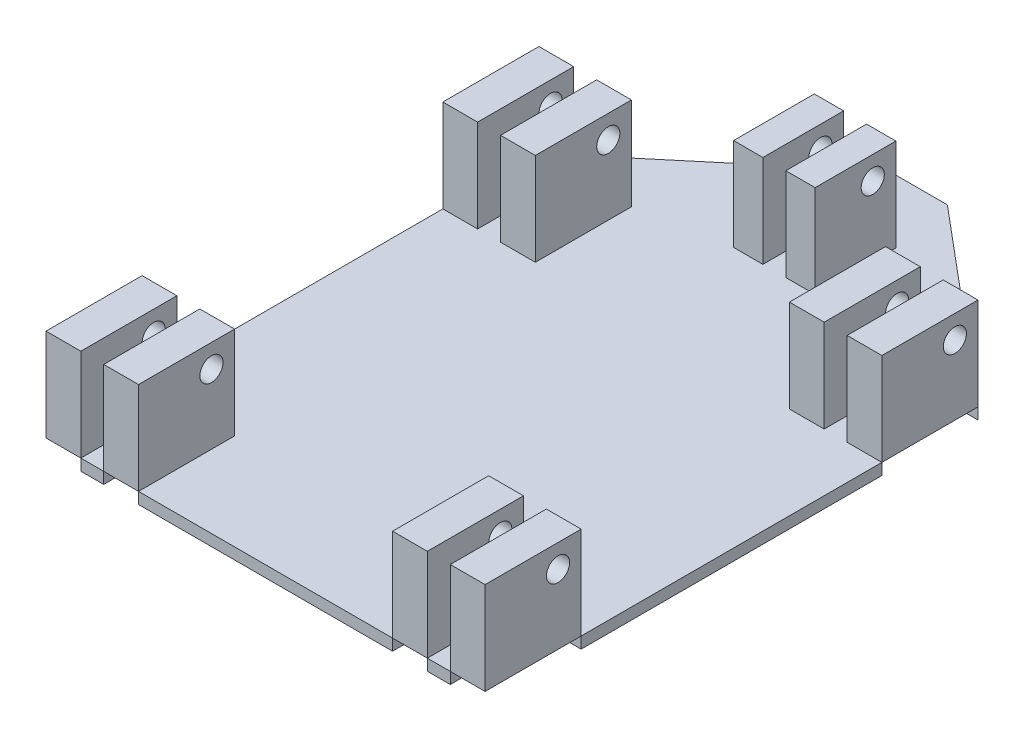
SolidWorks part; units mm, degrees
ref_plane "Front Plane" through (0, 0, 0) normal (0, 0, 1) x (1, 0, 0)
ref_plane "Top Plane" through (0, 0, 0) normal (0, 1, 0) x (1, 0, 0)
ref_plane "Right Plane" through (0, 0, 0) normal (1, 0, 0) x (0, 0, -1)
sketch "Sketch3" plane through (0, 0, 0) normal (0, 1, 0) x (1, 0, 0)
  line L0 (0, -106.5039) -> (0, 106.5039) construction
  line L1 (94.869, -106.5039) -> (-94.869, -106.5039)
  line L2 (94.869, -106.5039) -> (94.869, 106.5039)
  line L3 (94.869, 106.5039) -> (-94.869, 106.5039)
  line L4 (-94.869, -106.5039) -> (-94.869, 106.5039)
  line L5 (94.869, -106.5039) -> (-94.869, 106.5039) construction
  line L6 (94.869, 106.5039) -> (-94.869, -106.5039) construction
  line L7 (-94.869, 106.5039) -> (-79.8332, 106.5039)
  line L8 (-94.869, 106.5039) -> (-94.869, 64.9763)
  line L9 (-94.869, 64.9763) -> (-79.8332, 64.9763)
  line L10 (-79.8332, 106.5039) -> (-79.8332, 64.9763)
  line L11 (-94.869, 106.5039) -> (-79.8332, 64.9763) construction
  line L12 (-94.869, 64.9763) -> (-79.8332, 106.5039) construction
  line L13 (-74.8802, -106.5039) -> (74.8802, -106.5039)
  line L14 (74.8802, -106.5039) -> (74.8802, 106.5039) construction
  line L15 (-94.869, 0) -> (94.869, 0) construction
  line L16 (-74.8802, -106.5039) -> (-74.8802, 106.5039) construction
  line L17 (-54.8913, 64.9763) -> (-69.9272, 64.9763)
  line L18 (-69.9272, 106.5039) -> (-69.9272, 64.9763)
  line L19 (-54.8913, 106.5039) -> (-69.9272, 106.5039)
  line L20 (-54.8913, 106.5039) -> (-54.8913, 64.9763)
  line L21 (-54.8913, -106.5039) -> (-54.8913, -64.9763)
  line L22 (-54.8913, -106.5039) -> (-69.9272, -106.5039)
  line L23 (-69.9272, -106.5039) -> (-69.9272, -64.9763)
  line L24 (-54.8913, -64.9763) -> (-69.9272, -64.9763)
  line L25 (-94.869, -64.9763) -> (-79.8332, -64.9763)
  line L26 (-79.8332, -106.5039) -> (-79.8332, -64.9763)
  line L27 (-94.869, -106.5039) -> (-79.8332, -106.5039)
  line L28 (-94.869, -106.5039) -> (-94.869, -64.9763)
  line L29 (94.869, -106.5039) -> (79.8332, -106.5039)
  line L30 (79.8332, -106.5039) -> (79.8332, -64.9763)
  line L31 (94.869, -64.9763) -> (79.8332, -64.9763)
  line L32 (94.869, -106.5039) -> (94.869, -64.9763)
  line L33 (54.8913, -106.5039) -> (69.9272, -106.5039)
  line L34 (69.9272, -106.5039) -> (69.9272, -64.9763)
  line L35 (54.8913, -64.9763) -> (69.9272, -64.9763)
  line L36 (54.8913, -106.5039) -> (54.8913, -64.9763)
  line L37 (54.8913, 106.5039) -> (54.8913, 64.9763)
  line L38 (54.8913, 106.5039) -> (69.9272, 106.5039)
  line L39 (69.9272, 106.5039) -> (69.9272, 64.9763)
  line L40 (54.8913, 64.9763) -> (69.9272, 64.9763)
  line L41 (94.869, 64.9763) -> (79.8332, 64.9763)
  line L42 (79.8332, 106.5039) -> (79.8332, 64.9763)
  line L43 (94.869, 106.5039) -> (79.8332, 106.5039)
  line L44 (94.869, 106.5039) -> (94.869, 64.9763)
  line L45 (-94.869, 106.5039) -> (-12.6358, 175.5058)
  line L46 (-12.6358, 175.5058) -> (12.6358, 175.5058)
  line L47 (12.6358, 175.5058) -> (94.869, 106.5039)
  line L48 (-45.1068, 148.2593) -> (45.1068, 148.2593)
  line L49 (17.6268, 113.3764) -> (4.953, 148.2593) construction
  line L50 (-17.6268, 148.2593) -> (-4.953, 148.2593)
  line L51 (-17.6268, 148.2593) -> (-17.6268, 113.3764)
  line L52 (-17.6268, 113.3764) -> (-4.953, 113.3764)
  line L53 (-4.953, 148.2593) -> (-4.953, 113.3764)
  line L54 (-17.6268, 148.2593) -> (-4.953, 113.3764) construction
  line L55 (-17.6268, 113.3764) -> (-4.953, 148.2593) construction
  line L56 (17.6268, 148.2593) -> (4.953, 113.3764) construction
  line L57 (17.6268, 113.3764) -> (4.953, 113.3764)
  line L58 (4.953, 148.2593) -> (4.953, 113.3764)
  line L59 (17.6268, 148.2593) -> (4.953, 148.2593)
  line L60 (17.6268, 148.2593) -> (17.6268, 113.3764)
  point P0 (0, 0)
  point P9 (-87.3511, 85.7401)
  point P15 (0, -106.5039)
  point P52 (-11.2899, 130.8178)
  point P53 (11.2899, 130.8178)
  dimension "D1" = 189.738
  dimension "D2" = 9.906
  dimension "D3" = 40
  dimension "D4" = 40
  dimension "D5" = 9.906
extrude "Boss-Extrude1" add sketch "Sketch3" along normal blind 40 contours L53 L48 L51 L52 | L10 L3 L4 L9 | L20 L3 L18 L17 | L37 L40 L39 L3 | L3 L42 L41 L2 | L1 L26 L25 L4 | L21 L24 L23 L13 | L36 L13 L34 L35 | L2 L31 L30 L1 | L60 L57 L58 L59 region at (87.3511, 0, 85.7401) region at (87.3511, 0, -85.7401) region at (62.4092, 0, 85.7401) region at (-62.4092, 0, 85.7401) region at (62.4092, 0, -85.7401) region at (-62.4092, 0, -85.7401) region at (-11.2899, 0, -130.8178) region at (-87.3511, 0, 85.7401) region at (-87.3511, 0, -85.7401)
extrude "Boss-Extrude3" add sketch "Sketch3<5>" against normal blind 4.92 separate body contours L42 L3 L39 L40 L37 L20 L17 L18 L10 L9 L4 L25 L26 L1 L23 L24 L21 L36 L35 L34 L30 L31 L2 L41 | L48 L60 L57 L58 L53 L52 L51 L45 L3 L47 | L45 L48 L47 L46 region at (0, 0, 0) region at (0, 0, -123.854) region at (0, 0, -159.3289)
sketch "Sketch3<5>" plane through (0, 0, 0) normal (0, 1, 0) x (1, 0, 0) same geometry as "Sketch3"
sketch "Sketch4" plane through (-94.869, 0, 0) normal (-1, 0, 0) x (0, 0, 1)
  line L0 (-106.5039, 40) -> (-106.5039, 0) construction
  line L1 (-64.9763, 40) -> (-106.5039, 40) construction
  circle A0 centre (-96.5039, 30) radius 5
  dimension "D1" = 10
  dimension "D2" = 10
sketch "Sketch5" plane through (-17.6268, 0, 0) normal (-1, 0, 0) x (0, 0, 1)
  line L0 (-148.2593, 40) -> (-148.2593, 0) construction
  line L1 (-148.2593, 40) -> (-113.3764, 40) construction
  circle A0 centre (-138.2593, 30) radius 5
  dimension "D1" = 10
  dimension "D2" = 10
sketch "Sketch6" plane through (-94.869, 0, 0) normal (-1, 0, 0) x (0, 0, 1)
  line L0 (64.9763, 40) -> (64.9763, 0) construction
  line L1 (106.5039, 40) -> (64.9763, 40) construction
  circle A0 centre (74.9763, 30) radius 5
  dimension "D1" = 10
  dimension "D2" = 10
extrude "Cut-Extrude1" cut sketch "Sketch6" against normal up to vertex (189.738 mm away) up to point (94.869, 40, 64.9763)
extrude "Cut-Extrude2" cut sketch "Sketch5" against normal blind 203.294
extrude "Cut-Extrude3" cut sketch "Sketch4" against normal blind 203.294 contours A0
